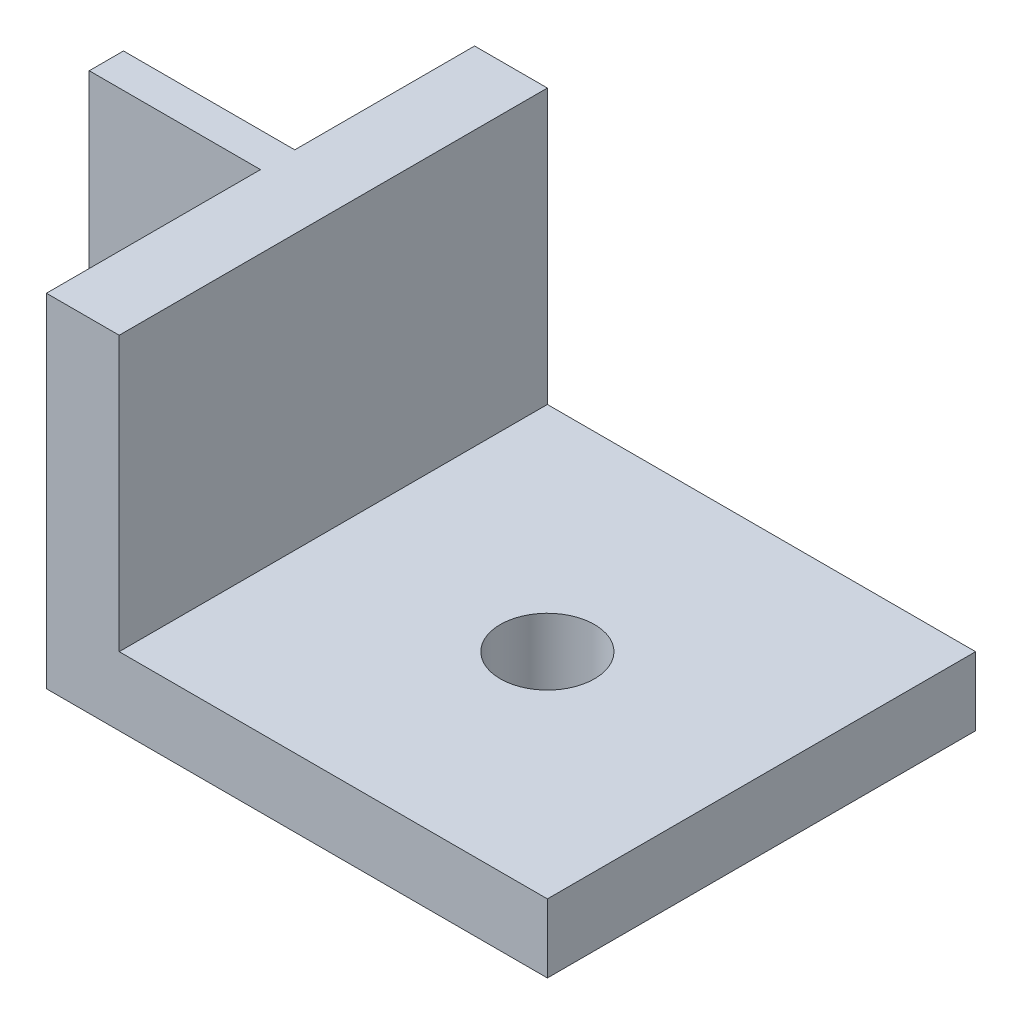
SolidWorks part; units mm, degrees
ref_plane "前视基准面" through (0, 0, 0) normal (0, 0, 1) x (1, 0, 0)
ref_plane "上视基准面" through (0, 0, 0) normal (0, 1, 0) x (1, 0, 0)
ref_plane "右视基准面" through (0, 0, 0) normal (1, 0, 0) x (0, 0, -1)
other "Configuration Table"
sketch "草图1" plane through (0, 0, 0) normal (0, 1, 0) x (1, 0, 0)
  line L1 (-12.5, 12.5) -> (12.5, 12.5)
  line L2 (-12.5, 12.5) -> (-12.5, -12.5)
  line L3 (-12.5, -12.5) -> (12.5, -12.5)
  line L4 (12.5, 12.5) -> (12.5, -12.5)
  line L5 (-12.5, 12.5) -> (12.5, -12.5) construction
  line L6 (-12.5, -12.5) -> (12.5, 12.5) construction
  line L7 (-12.5, -12.5) -> (-27.5, -12.5)
  line L8 (-12.5, -12.5) -> (-12.5, 12.5)
  line L9 (-12.5, 12.5) -> (-27.5, 12.5)
  line L10 (-27.5, -12.5) -> (-27.5, 12.5)
  circle A0 centre (0, 0) radius 2.75
  point P0 (0, 0)
  dimension "D4" = 5.5
  dimension "D1" = 25
  dimension "D2" = 25
  dimension "D3" = 15
extrude "凸台-拉伸1" add sketch "草图1" along normal blind 4 contours L4 L1 L2 L3 A0 region at (0, 0, -12.1464)
extrude "凸台-拉伸2" add sketch "草图1<3>" along normal blind 20 contours L10 L7 L2 L9 region at (-20, 0, 0)
sketch "草图1<3>" plane through (0, 0, 0) normal (0, 1, 0) x (1, 0, 0) same geometry as "草图1"
sketch "草图2" plane through (0, 20, 0) normal (0, 1, 0) x (1, 0, 0)
  line L0 (-12.5, -12.5) -> (-27.5, -12.5) construction
  line L1 (-27.5, 12.5) -> (-16.7491, 12.5)
  line L2 (-27.5, 12.5) -> (-27.5, -12.5)
  line L3 (-27.5, -12.5) -> (-16.7491, -12.5)
  line L4 (-16.7491, 12.5) -> (-16.7491, -12.5)
extrude "切除-拉伸1" cut sketch "草图2" against normal blind 43
sketch "草图3" plane through (0, 20, 0) normal (0, 1, 0) x (1, 0, 0)
  line L0 (-16.7491, -12.5) -> (-16.7491, 12.5) construction
  line L1 (-16.7491, 0) -> (-26.7491, 0)
  line L2 (-16.7491, 0) -> (-16.7491, 2)
  line L3 (-16.7491, 2) -> (-26.7491, 2)
  line L4 (-26.7491, 0) -> (-26.7491, 2)
  dimension "D1" = 10
  dimension "D2" = 2
extrude "凸台-拉伸4" add sketch "草图3" against normal up to surface (20 mm away) up to face at (0, 0, 2.75)
